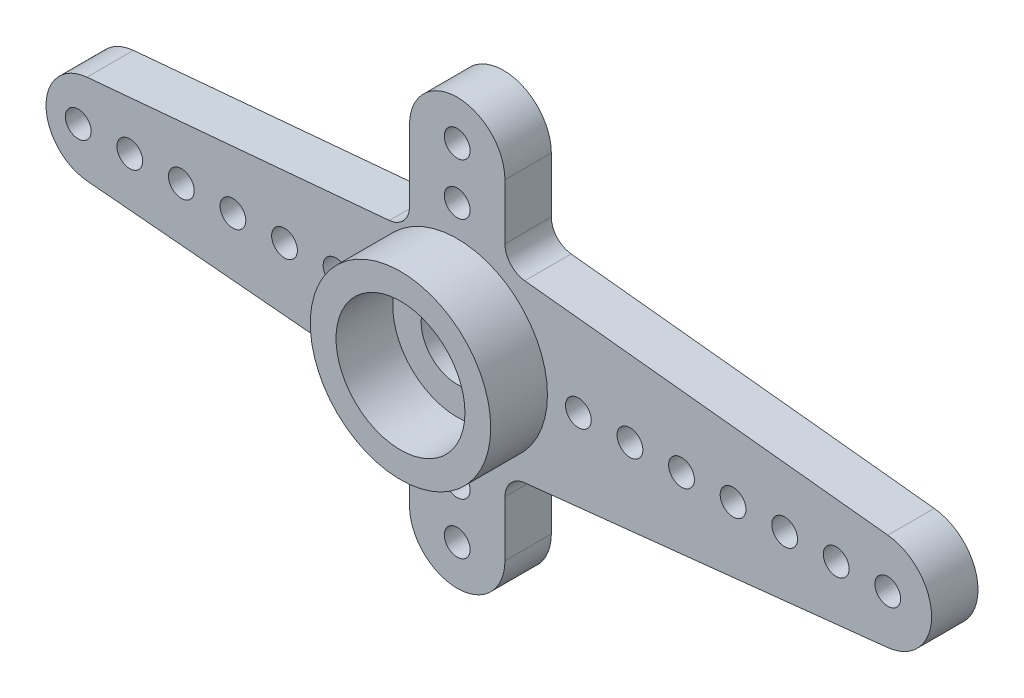
SolidWorks part; units mm, degrees
ref_plane "Front Plane" through (0, 0, 0) normal (0, 0, 1) x (1, 0, 0)
ref_plane "Top Plane" through (0, 0, 0) normal (0, 1, 0) x (1, 0, 0)
ref_plane "Right Plane" through (0, 0, 0) normal (1, 0, 0) x (0, 0, -1)
sketch "Sketch1" plane through (0, 0, 0) normal (0, 0, 1) x (1, 0, 0)
  line L0 (-1.7799, 22.3875) -> (569.8137, 43.9463) construction
  line L1 (14.7158, 13.285) -> (14.7158, 16.035)
  line L2 (18.4158, 16.035) -> (18.4158, 13.885)
  line L3 (19.1852, 13.0289) -> (33.2676, 11.5243)
  line L4 (33.2676, 7.7458) -> (19.1852, 6.2411)
  line L5 (18.4158, 5.385) -> (18.4158, 3.235)
  line L6 (14.7158, 3.235) -> (14.7158, 5.985)
  line L7 (13.9316, 6.8425) -> (2.2097, 7.892)
  line L8 (2.2097, 11.378) -> (13.9316, 12.4275)
  circle A0 centre (11.8658, 9.635) radius 0.5
  circle A1 centre (21.2658, 9.635) radius 0.5
  circle A2 centre (16.5658, 9.635) radius 1.4
  circle A4 centre (16.5658, 14.335) radius 0.5
  circle A5 centre (16.5658, 4.935) radius 0.5
  arc A6 (14.7158, 16.035) -> (18.4158, 16.035) centre (16.5658, 16.035) cw
  arc A7 (18.4158, 13.885) -> (19.1852, 13.0289) centre (19.2767, 13.885) ccw
  arc A8 (33.2676, 11.5243) -> (33.2676, 7.7458) centre (33.0658, 9.635) cw
  arc A9 (19.1852, 6.2411) -> (18.4158, 5.385) centre (19.2767, 5.385) ccw
  arc A10 (18.4158, 3.235) -> (14.7158, 3.235) centre (16.5658, 3.235) cw
  arc A11 (14.7158, 5.985) -> (13.9316, 6.8425) centre (13.8548, 5.985) ccw
  arc A12 (2.2097, 7.892) -> (2.2097, 11.378) centre (2.3658, 9.635) cw
  arc A13 (14.7158, 13.285) -> (13.9316, 12.4275) centre (13.8548, 13.285) cw
  dimension "D1" = 1
  dimension "D4" = 2.8
  dimension "D10" = 1.75
  dimension "D11" = 0.861
  dimension "D15" = 1.85
  dimension "D16" = 1.9
  dimension "D2" = 16.5658
  dimension "D3" = 9.635
  dimension "D6" = 4.7
  dimension "D7" = 4.7
  dimension "D8" = 4.7
  dimension "D9" = 4.7
  dimension "D12" = 9.5
  dimension "D13" = 6.4
  dimension "D14" = 6.4
  dimension "D17" = 16.5
  dimension "D18" = 2.75
  dimension "D19" = 2.15
extrude "Boss-Extrude1" add sketch "Sketch1" along normal blind 1.8 contours L1 A13 L8 A12 L7 A11 L6 A10 L5 A9 L4 A8 L3 A7 L2 A6 A0 A1 A4 A5 region at (15.0968, 14.66, 0)
ref_axis "Axis1" through (0, 43.2309, 0) along (0, -1, 0)
ref_axis "Axis2" through (36.6833, 0, 0) along (-1, 0, 0)
pattern_linear "LPattern1" count 6 spacing 2 along (-1, 0, 0) of face at (12.3658, 9.635, 1.8)
pattern_linear "LPattern2" count 7 spacing 2 along (1, 0, 0) of face at (21.7658, 9.635, 1.8)
pattern_linear "LPattern3" count 2 spacing 2 along (0, 1, 0) of face at (17.0658, 14.335, 1.8)
pattern_linear "LPattern4" count 2 spacing 2 along (0, -1, 0) of face at (17.0658, 4.935, 1.8)
sketch "Sketch2" plane through (0, 0, 0) normal (0, 0, -1) x (-1, 0, 0)
  circle A0 centre (-16.5658, 9.635) radius 2.5
  dimension "D1" = 5
extrude "Cut-Extrude1" cut sketch "Sketch2" against normal blind 1
sketch "Sketch3" plane through (0, 0, 1.8) normal (0, 0, 1) x (1, 0, 0)
  circle A0 centre (16.5658, 9.635) radius 3.5
  circle A1 centre (16.5658, 9.635) radius 2.5
  dimension "D1" = 7
  dimension "D2" = 5
extrude "Boss-Extrude2" add sketch "Sketch3" along normal blind 2.2
